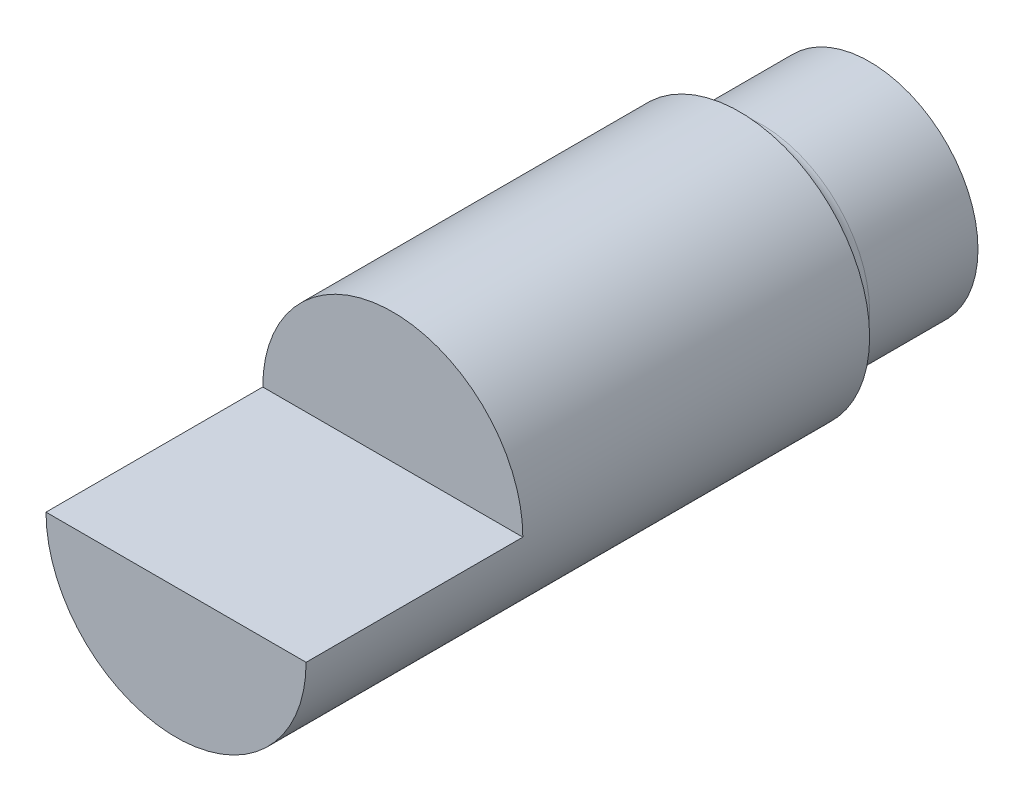
SolidWorks part; units mm, degrees
material "Gray Cast Iron"
ref_plane "Front Plane" through (0, 0, 0) normal (0, 0, 1) x (1, 0, 0)
ref_plane "Top Plane" through (0, 0, 0) normal (0, 1, 0) x (1, 0, 0)
ref_plane "Right Plane" through (0, 0, 0) normal (1, 0, 0) x (0, 0, -1)
sketch "Sketch1" plane through (0, 0, 0) normal (0, 0, 1) x (1, 0, 0)
  circle A0 centre (0, 0) radius 15
  dimension "D1" = 30
extrude "Boss-Extrude1" add sketch "Sketch1" along normal blind 40
sketch "Sketch2" plane through (0, 0, 40) normal (0, 0, 1) x (1, 0, 0)
  line L0 (-15, 0) -> (15, 0)
  arc A0 (-15, 0) -> (15, 0) centre (0, 0) ccw
  point P6 (0, 0)
  dimension "D1" = 30
extrude "Boss-Extrude2" add sketch "Sketch2" along normal blind 25 contours A0 L0
sketch "Sketch3" plane through (0, 0, 0) normal (0, 0, -1) x (-1, 0, 0)
  circle A0 centre (0, 0) radius 12.5
  dimension "D1" = 25
extrude "Boss-Extrude3" add sketch "Sketch3" along normal blind 15 contours A0
fillet "Fillet1" radius 2.5 1 edges at (-12.5, 0, 0)
